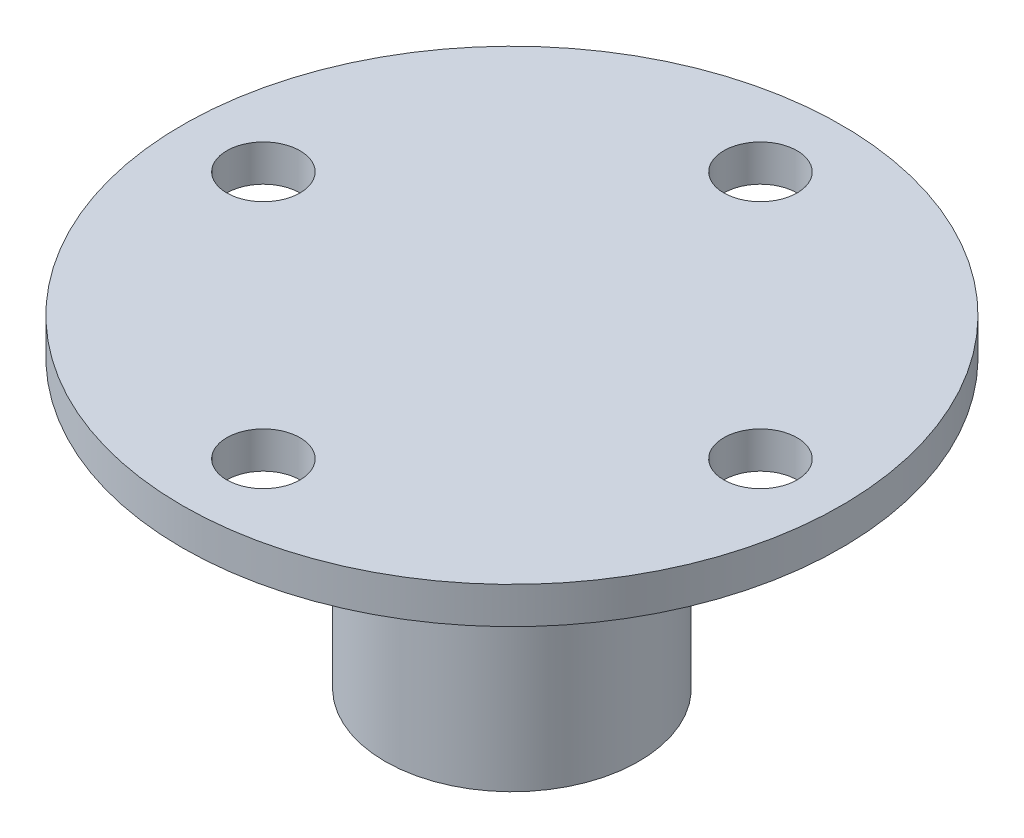
SolidWorks part; units mm, degrees
ref_plane "Front Plane" through (0, 0, 0) normal (0, 0, 1) x (1, 0, 0)
ref_plane "Top Plane" through (0, 0, 0) normal (0, 1, 0) x (1, 0, 0)
ref_plane "Right Plane" through (0, 0, 0) normal (1, 0, 0) x (0, 0, -1)
sketch "Sketch1" plane through (0, 0, 0) normal (0, 1, 0) x (1, 0, 0)
  line L0 (0, 0) -> (21.548, 0)
  line L6 (-6.7175, -3.8891) -> (-3.8891, -6.7175)
  line L7 (-3.8891, -6.7175) -> (-2.5858, -5.4142)
  line L8 (-6.7175, -3.8891) -> (-5.4142, -2.5858)
  circle A0 centre (0, 0) radius 28.575
  circle A1 centre (0, 0) radius 11
  circle A2 centre (21.548, 0) radius 3.175
  circle A3 centre (0, 0) radius 6
  circle A4 centre (0, -21.548) radius 3.175
  circle A5 centre (-21.548, 0) radius 3.175
  circle A6 centre (0, 21.548) radius 3.175
  point P20 (0, 0)
  dimension "D1" = 6.35
  dimension "D2" = 4
  dimension "D3" = 12
  dimension "D4" = 4
extrude "Boss-Extrude1" add sketch "Sketch1" along normal blind 3.175 contours A0 A6 A5 A4 A2 A1 region at (-27.7668, 0, 0)
extrude "Boss-Extrude2" add sketch "Sketch1<4>" along normal blind 3.175 contours A3 | A3 L8 L6 L7 | A3 A1 L7 L6 L8 region at (-10.6889, 0, 0) region at (3.1099, 0, 4.9316) region at (-4.7307, 0, 4.7307)
sketch "Sketch1<4>" plane through (0, 0, 0) normal (0, 1, 0) x (1, 0, 0) same geometry as "Sketch1"
extrude "Boss-Extrude3" add sketch "Sketch1<5>" against normal blind 24.825 contours A3 A1 L7 L6 L8 region at (-10.6889, 0, 0)
sketch "Sketch1<5>" plane through (0, 0, 0) normal (0, 1, 0) x (1, 0, 0) same geometry as "Sketch1"
